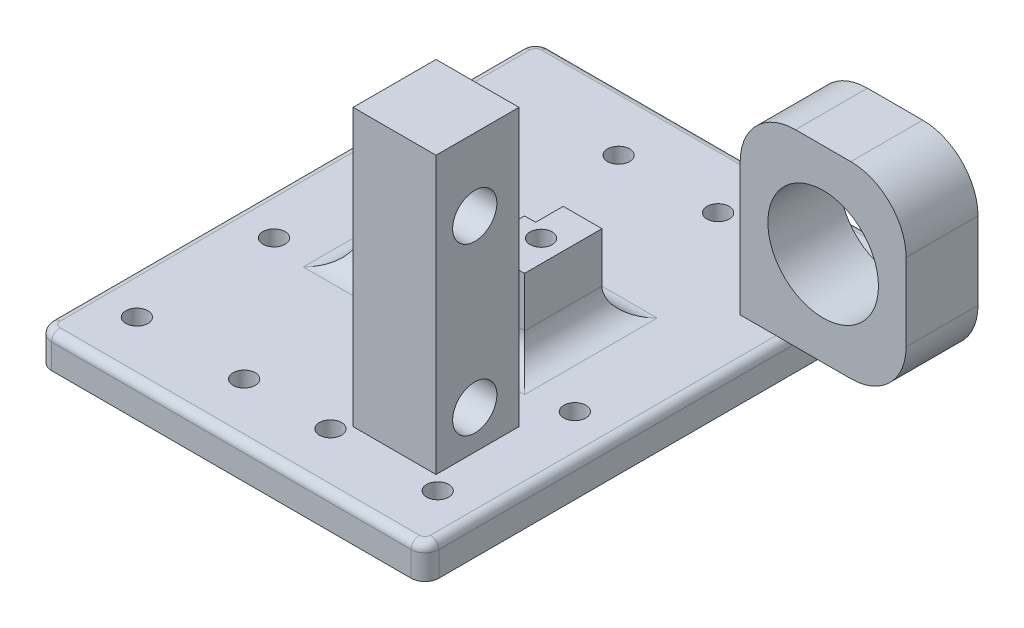
SolidWorks part; units mm, degrees
ref_plane "Front Plane" through (0, 0, 0) normal (0, 0, 1) x (1, 0, 0)
ref_plane "Top Plane" through (0, 0, 0) normal (0, 1, 0) x (1, 0, 0)
ref_plane "Right Plane" through (0, 0, 0) normal (1, 0, 0) x (0, 0, -1)
sketch "Sketch1" plane through (0, 0, 0) normal (0, 1, 0) x (1, 0, 0)
  line L0 (-8.0156, -1.4008) -> (61.9844, -1.4008)
  line L1 (-8.0156, 43.5992) -> (61.9844, 43.5992)
  line L2 (-8.0156, 43.5992) -> (-8.0156, -46.4008)
  line L3 (-8.0156, -46.4008) -> (61.9844, -46.4008)
  line L4 (61.9844, 43.5992) -> (61.9844, -46.4008)
  line L5 (26.9844, 43.5992) -> (26.9844, -46.4008)
  line L6 (9.4844, -1.4008) -> (9.4844, -46.4008)
  line L7 (-8.0156, -23.9008) -> (61.9844, -23.9008)
  circle A0 centre (17.9844, 32.5992) radius 3
  circle A1 centre (17.9844, 32.5992) radius 2
  circle A2 centre (18.095, 8.5992) radius 3
  circle A3 centre (18.095, 8.5992) radius 2
  circle A4 centre (35.8739, 8.5992) radius 2
  circle A5 centre (35.8739, 8.5992) radius 3
  circle A6 centre (35.9844, 32.5992) radius 2
  circle A7 centre (35.9844, 32.5992) radius 3
  circle A8 centre (19.1844, -11.5008) radius 2
  circle A9 centre (19.1844, -11.5008) radius 3
  circle A10 centre (-0.2156, -11.5008) radius 3
  circle A11 centre (-0.2156, -11.5008) radius 2
  circle A12 centre (-0.2156, -36.3008) radius 2
  circle A13 centre (19.1844, -36.3008) radius 3
  circle A14 centre (19.1844, -36.3008) radius 2
  circle A15 centre (-0.2156, -36.3008) radius 3
  circle A16 centre (54.1844, -36.3008) radius 2
  circle A17 centre (54.1844, -36.3008) radius 3
  circle A18 centre (34.7844, -36.3008) radius 2
  circle A19 centre (34.7844, -36.3008) radius 3
  circle A20 centre (34.7844, -11.5008) radius 3
  circle A21 centre (34.7844, -11.5008) radius 2
  circle A22 centre (54.1844, -11.5008) radius 2
  circle A23 centre (54.1844, -11.5008) radius 3
  dimension "D3" = 9
  dimension "D1" = 90
  dimension "D2" = 70
  dimension "D4" = 11
  dimension "D5" = 24
  dimension "D6" = 10.1
  dimension "D7" = 7.8
  dimension "D8" = 17.5
  dimension "D9" = 22.5
extrude "Boss-Extrude1" add sketch "Sketch1" along normal blind 6 contours L5 L1 L2 L0 A2 A0 | L1 L5 L0 L4 A5 A7 | A7 A6 | A0 A1 | A2 A3 | A5 A4 | L7 L6 L3 L5 A13 | L6 L7 L5 L0 A9 | L2 L7 L6 L0 A10 | L5 L7 L4 L0 A20 A23 | L7 L5 L3 L4 A17 A19 | L7 L2 L3 L6 A15 | A10 A11 | A9 A8 | A20 A21 | A23 A22 | A17 A16 | A13 A14 | A15 A12 | A19 | A18 region at (9.1658, 0, -21.1178) region at (0.7344, 0, 1.6858) region at (18.2344, 0, 1.6858) region at (0.7344, 0, 24.1858) region at (44.803, 0, -21.1178) region at (44.4844, 0, 12.7397) region at (18.2344, 0, 24.1858) region at (44.4844, 0, 35.0618) region at (15.0693, 0, -32.5992) region at (15.1799, 0, -8.5992) region at (32.9587, 0, -8.5992) region at (33.0693, 0, -32.5992) region at (16.2693, 0, 11.5008) region at (-3.1307, 0, 11.5008) region at (16.2693, 0, 36.3008) region at (-3.1307, 0, 36.3008) region at (51.2693, 0, 36.3008) region at (31.8693, 0, 11.5008) region at (51.2693, 0, 11.5008)
sketch "Sketch3" plane through (0, 6, 0) normal (0, 1, 0) x (1, 0, 0)
  line L0 (26.9844, 43.5992) -> (26.9844, -46.4008)
  line L1 (11.9844, 5.5992) -> (41.9844, 5.5992)
  line L2 (11.9844, 5.5992) -> (11.9844, -8.4008)
  line L3 (11.9844, -8.4008) -> (41.9844, -8.4008)
  line L4 (41.9844, 5.5992) -> (41.9844, -8.4008)
  line L5 (-8.0156, 43.5992) -> (61.9844, 43.5992) construction
  line L6 (-8.0156, -46.4008) -> (61.9844, -46.4008) construction
  line L7 (-8.0156, -1.4008) -> (61.9844, -1.4008)
  line L8 (-8.0156, 43.5992) -> (-8.0156, -46.4008) construction
  line L9 (61.9844, 43.5992) -> (61.9844, -46.4008) construction
  dimension "D1" = 14
  dimension "D2" = 30
  dimension "D3" = 7
  dimension "D4" = 15
extrude "Boss-Extrude2" add sketch "Sketch3" along normal blind 14 contours L2 L7 L0 L1 | L0 L7 L4 L1 | L7 L0 L3 L4 | L7 L2 L3 L0 region at (34.4844, 6, -2.0992) region at (19.4844, 6, -2.0992) region at (34.4844, 6, 4.9008) region at (19.4844, 6, 4.9008)
fillet "Fillet1" radius 2.5 4 edges at (-8.0156, 3, -43.5992) (61.9844, 3, -43.5992) (61.9844, 3, 46.4008) (-8.0156, 3, 46.4008)
fillet "Fillet2" radius 1.5 8 edges at (26.9844, 6, -43.5992) (-7.2833, 6, 45.6685) (61.2522, 6, 45.6685) (26.9844, 6, 46.4008) (61.2522, 6, -42.867) (61.9844, 6, 1.4008) (-7.2833, 6, -42.867) (-8.0156, 6, 1.4008)
sketch "Sketch4" plane through (0, 20, 0) normal (0, 1, 0) x (1, 0, 0)
  line L0 (26.9844, 42.0992) -> (26.9844, -44.9008)
  line L1 (59.4844, 42.0992) -> (-5.5156, 42.0992) construction
  line L2 (-5.5156, -44.9008) -> (59.4844, -44.9008) construction
  line L3 (-6.5156, -1.4008) -> (60.4844, -1.4008)
  line L4 (-6.5156, 41.0992) -> (-6.5156, -43.9008) construction
  line L5 (60.4844, -43.9008) -> (60.4844, 41.0992) construction
  circle A0 centre (15.9844, -1.4008) radius 2
  circle A1 centre (37.9844, -1.4008) radius 2
  dimension "D1" = 11
extrude "Cut-Extrude1" cut sketch "Sketch4" against normal blind 22 contours L3 A0 | L3 A0 | A1 L3 | A1 L3 region at (15.9844, 20, 0.552) region at (37.9844, 20, 0.552) region at (37.9844, 20, 2.2496) region at (15.9844, 20, 2.2496)
sketch "Sketch5" plane through (0, 0, -5.5992) normal (0, 0, -1) x (-1, 0, 0)
  line L0 (-11.9844, 20) -> (-41.9844, 20) construction
  line L1 (-34.9844, 20) -> (-18.9844, 20)
  circle A0 centre (-26.9844, 20) radius 8
  circle A1 centre (-26.9844, 20) radius 6
extrude "Cut-Extrude2" cut sketch "Sketch5" against normal blind 22 contours A1
sketch "Sketch6" plane through (0, 0, -5.5992) normal (0, 0, -1) x (-1, 0, 0)
  line L0 (-18.9844, 20) -> (-34.9844, 20)
  circle A0 centre (-26.9844, 20) radius 8
  circle A1 centre (-26.9844, 20) radius 6
  circle A2 centre (-26.9844, 20) radius 6
  circle A3 centre (-26.9844, 20) radius 8
  arc M1 (-20.9844, 20) -> (-32.9844, 20) centre (-26.9844, 20) cw
  line M2 (-32.9844, 20) -> (-41.9844, 20)
  line M6 (-11.9844, 20) -> (-20.9844, 20)
  dimension "D1" = 12
  dimension "D2" = 16
extrude "Cut-Extrude4" cut sketch "Sketch6" against normal blind 5 contours A0 M2 M6 M1 region at (26.9844, 12.1789, -5.5992)
sketch "Sketch9" plane through (0, 0, 8.4008) normal (0, 0, 1) x (1, 0, 0)
  circle A0 centre (26.9844, 20) radius 6
  circle A1 centre (26.9844, 20) radius 8
extrude "Cut-Extrude5" cut sketch "Sketch9" against normal blind 5
fillet "Fillet3" radius 5 4 edges at (26.9844, 6, 8.4008) (11.9844, 6, 1.4008) (26.9844, 6, -5.5992) (41.9844, 6, 1.4008)
sketch "Sketch10" plane through (0, 6, 0) normal (0, 1, 0) x (1, 0, 0)
  line L0 (53.9844, 42.0992) -> (53.9844, -44.9008)
  line L1 (59.4844, 42.0992) -> (-5.5156, 42.0992) construction
  line L2 (-5.5156, -44.9008) -> (59.4844, -44.9008) construction
  line L3 (26.9844, 43.5992) -> (26.9844, -46.4008)
  line L4 (-5.5156, 43.5992) -> (59.4844, 43.5992) construction
  line L5 (59.4844, -46.4008) -> (-5.5156, -46.4008) construction
  line L6 (26.9844, -1.4008) -> (60.4844, -1.4008)
  line L7 (53.9844, 31.5992) -> (83.9844, 31.5992)
  line L8 (53.9844, 31.5992) -> (53.9844, 18.5992)
  line L9 (53.9844, 18.5992) -> (83.9844, 18.5992)
  line L10 (83.9844, 31.5992) -> (83.9844, 18.5992)
  line L11 (60.4844, -43.9008) -> (60.4844, 41.0992) construction
  dimension "D1" = 27
  dimension "D2" = 30
  dimension "D3" = 20
  dimension "D4" = 13
extrude "Boss-Extrude5" add sketch "Sketch10" along normal blind 34 contours L7 L10 L9 L8
sketch "Sketch13" plane through (0, 0, -18.5992) normal (0, 0, 1) x (1, 0, 0)
  line L0 (68.9844, 40) -> (68.9844, 6)
  line L1 (53.9844, 40) -> (83.9844, 40) construction
  line L2 (60.4844, 6) -> (83.9844, 6) construction
  line L3 (53.9844, 23) -> (83.9844, 23)
  line L4 (53.9844, 40) -> (53.9844, 6) construction
  line L5 (83.9844, 40) -> (83.9844, 6) construction
  circle A0 centre (68.9844, 23) radius 10
extrude "Cut-Extrude6" cut sketch "Sketch13" against normal blind 34 contours L0 A0 L3 | L3 A0 L0 | L0 A0 L3 | L3 A0 L0 region at (73.2286, 27.2441, -18.5992) region at (64.7403, 27.2441, -18.5992) region at (73.2286, 18.7559, -18.5992) region at (64.7403, 18.7559, -18.5992)
fillet "Fillet5" radius 10 3 edges at (83.9844, 6, -25.0992) (53.9844, 40, -25.0992) (83.9844, 40, -25.0992)
sketch "Sketch14" plane through (0, 6, 0) normal (0, 1, 0) x (1, 0, 0)
  line L0 (-5.5156, -44.9008) -> (59.4844, -44.9008) construction
  line L1 (51.4844, -33.9008) -> (36.4844, -33.9008)
  line L2 (51.4844, -33.9008) -> (51.4844, -18.9008)
  line L3 (51.4844, -18.9008) -> (36.4844, -18.9008)
  line L4 (36.4844, -33.9008) -> (36.4844, -18.9008)
  line L5 (60.4844, -43.9008) -> (60.4844, 18.5992) construction
  dimension "D1" = 15
  dimension "D2" = 11
  dimension "D3" = 15
  dimension "D4" = 9
extrude "Boss-Extrude6" add sketch "Sketch14" along normal blind 50
sketch "Sketch15" plane through (51.4844, 0, 0) normal (1, 0, 0) x (0, 0, -1)
  line L0 (-33.9008, 6) -> (-18.9008, 6) construction
  line L1 (-33.9008, 56) -> (-33.9008, 6) construction
  circle A0 centre (-26.9008, 13) radius 4
  circle A1 centre (-26.9008, 43) radius 4
  dimension "D1" = 30
  dimension "D2" = 7
  dimension "D3" = 7
  dimension "D4" = 7
extrude "Cut-Extrude7" cut sketch "Sketch15" against normal blind 10
sketch "Sketch17" plane through (51.4844, 0, 0) normal (1, 0, 0) x (0, 0, -1)
  circle A0 centre (-26.9008, 43) radius 2.5
  circle A1 centre (-26.9008, 13) radius 2.5
extrude "Cut-Extrude8" cut sketch "Sketch17" against normal blind 30
